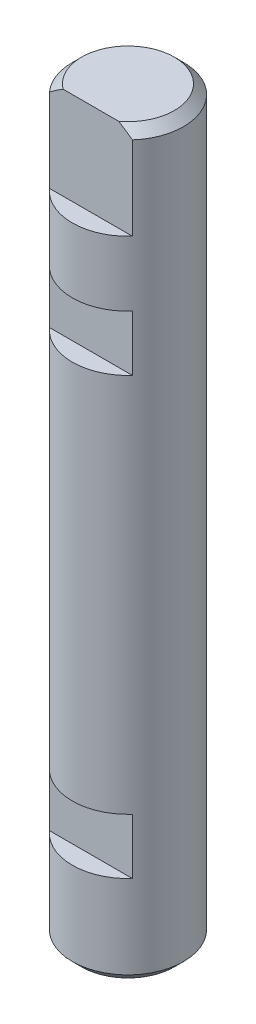
SolidWorks part; units mm, degrees
ref_plane "Alzado" through (0, 0, 0) normal (0, 0, 1) x (1, 0, 0)
ref_plane "Planta" through (0, 0, 0) normal (0, 1, 0) x (1, 0, 0)
ref_plane "Vista lateral" through (0, 0, 0) normal (1, 0, 0) x (0, 0, -1)
sketch "Croquis1" plane through (0, 0, 0) normal (0, 1, 0) x (1, 0, 0)
  circle A0 centre (0, 0) radius 3
  dimension "D1" = 6
extrude "Saliente-Extruir1" add sketch "Croquis1" along normal mid plane 40
sketch "Croquis3" plane through (0, 20, 0) normal (0, 1, 0) x (1, 0, 0)
  line L1 (-3.8744, -2) -> (4.3498, -2)
  line L2 (-3.8744, -2) -> (-3.8744, -3)
  line L3 (-3.8744, -3) -> (4.3498, -3)
  line L4 (4.3498, -2) -> (4.3498, -3)
  circle A0 centre (0, 0) radius 3 construction
  dimension "D1" = 1
  dimension "D2" = 2
extrude "Cortar-Extruir2" cut sketch "Croquis3" against normal blind 5 and the other way through all
sketch "Croquis4" plane through (0, 20, 0) normal (0, 1, 0) x (1, 0, 0)
  point P0 (0, 0)
ref_axis "Eje1" through (0, 20, 0) along (0, -1, 0)
sketch "Croquis8" plane through (0, 0, 2) normal (0, 0, 1) x (1, 0, 0)
  line L0 (-3, 20) -> (-3, -20) construction
  line L1 (-3, 11.5) -> (3, 11.5)
  line L2 (-3, 11.5) -> (-3, 8.5)
  line L3 (-3, 8.5) -> (3, 8.5)
  line L4 (3, 11.5) -> (3, 8.5)
  line L5 (3, -20) -> (3, 20) construction
  line L6 (2.2361, 15) -> (-2.2361, 15) construction
  line L7 (3, -20) -> (3, 20) construction
  line L8 (-3, -12) -> (3, -12)
  line L9 (-3, -12) -> (-3, -15)
  line L10 (-3, -15) -> (3, -15)
  line L11 (3, -12) -> (3, -15)
  line L12 (-3, -20) -> (3, -20) construction
  dimension "D1" = 3.5
  dimension "D2" = 3
  dimension "D3" = 5
  dimension "D4" = 3
extrude "Cortar-Extruir4" cut sketch "Croquis8" along normal blind 10
chamfer "Chaflán1" distance 0.5 angle 45 2 edges at (0, 20, -3) (0, -20, 3)
